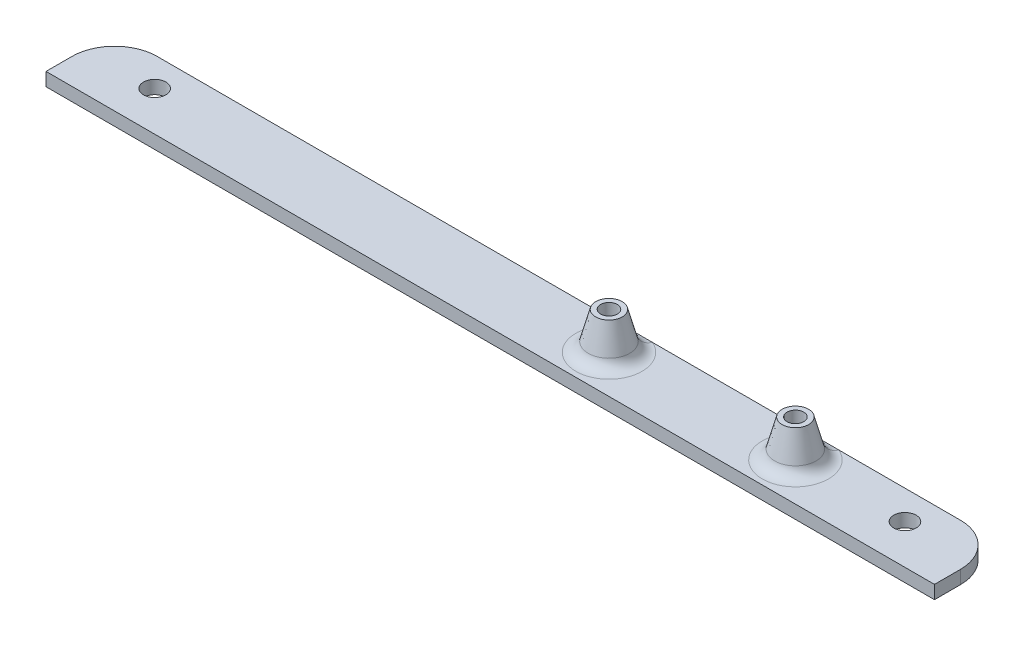
SolidWorks part; units mm, degrees
ref_plane "Front Plane" through (0, 0, 0) normal (0, 0, 1) x (1, 0, 0)
ref_plane "Top Plane" through (0, 0, 0) normal (0, 1, 0) x (1, 0, 0)
ref_plane "Right Plane" through (0, 0, 0) normal (1, 0, 0) x (0, 0, -1)
sketch "Backplane" plane through (0, 0, 0) normal (0, 1, 0) x (1, 0, 0)
  line L0 (-80.645, 87.63) -> (8.255, 87.63)
  line L1 (-106.045, -113.03) -> (106.045, -113.03)
  line L2 (-106.045, -113.03) -> (-106.045, 113.03)
  line L3 (-106.045, 113.03) -> (106.045, 113.03)
  line L4 (106.045, -113.03) -> (106.045, 113.03)
  line L5 (-106.045, -113.03) -> (106.045, 113.03) construction
  line L6 (-106.045, 113.03) -> (106.045, -113.03) construction
  line L7 (-106.045, 113.03) -> (-80.645, 113.03) construction
  line L8 (-106.045, 113.03) -> (-106.045, 87.63) construction
  line L9 (-106.045, 87.63) -> (-80.645, 87.63)
  line L10 (-80.645, 113.03) -> (-80.645, 87.63)
  line L11 (106.045, 113.03) -> (80.645, 113.03) construction
  line L12 (106.045, 113.03) -> (106.045, 87.63) construction
  line L13 (106.045, 87.63) -> (80.645, 87.63)
  line L14 (80.645, 113.03) -> (80.645, 87.63)
  line L15 (8.255, 87.63) -> (8.255, 113.03)
  line L16 (0, 0) -> (0, 113.03) construction
  line L17 (-86.8807, 106.1141) -> (86.8807, 106.1141)
  line L18 (-86.8807, 106.1141) -> (-89.5477, 106.1141)
  circle A0 centre (-89.5477, 106.1141) radius 2.667
  circle A1 centre (89.5477, 106.1141) radius 2.667
  point P0 (0, 0)
  point P19 (0, 106.1141)
  dimension "D5" = 5.334
  dimension "D1" = 212.09
  dimension "D2" = 226.06
  dimension "D3" = 173.7614
  dimension "D4" = 2.667
sketch "Protoboard1" plane through (0, 0, 0) normal (0, 1, 0) x (1, 0, 0)
  line L0 (59.2817, 74.5827) -> (59.2817, 49.1827) construction
  line L1 (-98.1983, 23.7827) -> (59.2817, 23.7827)
  line L2 (-98.1983, 23.7827) -> (-98.1983, 74.5827)
  line L3 (-98.1983, 74.5827) -> (59.2817, 74.5827)
  line L4 (59.2817, 23.7827) -> (59.2817, 74.5827)
  line L5 (-98.1983, 23.7827) -> (59.2817, 74.5827) construction
  line L6 (-98.1983, 74.5827) -> (59.2817, 23.7827) construction
  line L7 (-92.8897, 49.1827) -> (53.9731, 49.1827)
  line L8 (-19.4583, 49.1827) -> (-19.4583, 23.7827) construction
  line L9 (-92.8897, 49.1827) -> (-94.4772, 49.1827)
  circle A4 centre (-94.4772, 49.1827) radius 1.5875
  circle A5 centre (-94.4772, 49.1827) radius 5.5499
  circle A6 centre (55.5606, 49.1827) radius 1.5875
  circle A7 centre (55.5606, 49.1827) radius 5.5499
  circle A8 centre (-94.4772, 49.1827) radius 1.9939
  circle A9 centre (55.5606, 49.1827) radius 1.9939
  point P0 (-19.4583, 49.1827)
  point P9 (-19.4583, 49.1827)
  point P10 (-19.4583, 49.1827)
  dimension "D5" = 3.175
  dimension "D6" = 11.0998
  dimension "D7" = 3.9878
  dimension "D3" = 157.48
  dimension "D1" = 73.4314
  dimension "D2" = 1.5875
sketch "Protoboard2" plane through (0, 0, 0) normal (0, 1, 0) x (1, 0, 0)
  line L0 (58.42, 17.145) -> (58.42, -8.255) construction
  line L1 (-99.06, -33.655) -> (58.42, -33.655)
  line L2 (-99.06, -33.655) -> (-99.06, 17.145)
  line L3 (-99.06, 17.145) -> (58.42, 17.145)
  line L4 (58.42, -33.655) -> (58.42, 17.145)
  line L5 (-99.06, -33.655) -> (58.42, 17.145) construction
  line L6 (-99.06, 17.145) -> (58.42, -33.655) construction
  line L7 (-93.7514, -8.255) -> (53.1114, -8.255)
  line L8 (-20.32, -8.255) -> (-20.32, -33.655) construction
  line L9 (-93.7514, -8.255) -> (-95.3389, -8.255)
  circle A0 centre (-95.3389, -8.255) radius 1.5875
  circle A1 centre (-95.3389, -8.255) radius 5.5499
  circle A4 centre (-95.3389, -8.255) radius 1.9939
  circle A6 centre (54.6989, -8.255) radius 1.5875
  circle A7 centre (54.6989, -8.255) radius 1.9939
  circle A8 centre (54.6989, -8.255) radius 5.5499
  point P0 (-20.32, -8.255)
  point P9 (-20.32, -8.255)
  point P10 (-20.32, -8.255)
  dimension "D5" = 3.175
  dimension "D6" = 11.0998
  dimension "D7" = 3.9878
  dimension "D4" = 1.5875
  dimension "D1" = 157.48
  dimension "D3" = 73.4314
sketch "ADS1256" plane through (0, 0, 0) normal (0, 1, 0) x (1, 0, 0)
  line L0 (83.3697, -5.6387) -> (83.3697, 20.5868)
  line L1 (65.6786, -35.7758) -> (101.0608, -35.7758)
  line L2 (65.6786, -35.7758) -> (65.6786, 24.4984)
  line L3 (65.6786, 24.4984) -> (101.0608, 24.4984)
  line L4 (101.0608, -35.7758) -> (101.0608, 24.4984)
  line L5 (65.6786, -35.7758) -> (101.0608, 24.4984) construction
  line L6 (65.6786, 24.4984) -> (101.0608, -35.7758) construction
  line L7 (83.3697, 20.5868) -> (83.3697, 22.1743)
  line L8 (83.3697, 22.1743) -> (97.0222, 22.1743)
  line L9 (97.0222, 22.1743) -> (98.6097, 22.1743)
  line L10 (83.3697, -5.6387) -> (89.9657, -5.6387) construction
  circle A0 centre (98.6097, 22.1743) radius 1.5875
  circle A1 centre (98.6097, 22.1743) radius 5.5499
  circle A2 centre (68.1297, 22.1743) radius 1.5875
  circle A3 centre (68.1297, 22.1743) radius 5.5499
  circle A4 centre (98.6097, -33.4517) radius 5.5499
  circle A5 centre (98.6097, -33.4517) radius 1.5875
  circle A6 centre (68.1297, -33.4517) radius 1.5875
  circle A7 centre (68.1297, -33.4517) radius 5.5499
  circle A8 centre (98.6097, 22.1743) radius 1.9939
  circle A9 centre (68.1297, 22.1743) radius 1.9939
  circle A10 centre (98.6097, -33.4517) radius 1.9939
  circle A11 centre (68.1297, -33.4517) radius 1.9939
  point P0 (83.3697, -5.6387)
  dimension "D1" = 1.5875
  dimension "D2" = 1.5875
  dimension "D3" = 3.175
  dimension "D4" = 11.0998
  dimension "D5" = 3.9878
sketch "3V_Buck" plane through (0, 0, 0) normal (0, 1, 0) x (1, 0, 0)
  circle A0 centre (88.2115, 54.7666) radius 1.5875
  circle A1 centre (88.2115, 54.7666) radius 5.5499
  circle A2 centre (88.2115, 54.7666) radius 1.9939
  dimension "D1" = 3.175
  dimension "D2" = 11.0998
  dimension "D3" = 3.9878
sketch "Relay" plane through (0, 0, 0) normal (0, 1, 0) x (1, 0, 0)
  line L1 (16.3302, 81.8626) -> (66.6036, 81.8626)
  line L2 (16.3302, 81.8626) -> (16.3302, 108.1272)
  line L3 (16.3302, 108.1272) -> (66.6036, 108.1272)
  line L4 (66.6036, 81.8626) -> (66.6036, 108.1272)
  line L5 (16.3302, 81.8626) -> (66.6036, 108.1272) construction
  line L6 (16.3302, 108.1272) -> (66.6036, 81.8626) construction
  line L7 (41.4669, 94.9949) -> (41.4669, 104.2024)
  line L8 (41.4669, 104.2024) -> (41.4669, 105.7899)
  line L9 (41.4669, 105.7899) -> (62.1298, 105.7899)
  line L10 (62.1298, 105.7899) -> (63.7173, 105.7899)
  line L11 (41.4669, 94.9949) -> (31.7125, 94.9949) construction
  circle A0 centre (63.7173, 105.7899) radius 1.5875
  circle A1 centre (63.7173, 105.7899) radius 5.5499
  circle A2 centre (19.2165, 105.7899) radius 1.5875
  circle A3 centre (19.2165, 105.7899) radius 5.5499
  circle A4 centre (19.2165, 84.1999) radius 1.5875
  circle A5 centre (19.2165, 84.1999) radius 5.5499
  circle A6 centre (63.7173, 84.1999) radius 1.5875
  circle A7 centre (63.7173, 84.1999) radius 5.5499
  circle A8 centre (63.7173, 105.7899) radius 1.9939
  circle A9 centre (19.2165, 105.7899) radius 1.9939
  circle A10 centre (19.2165, 84.1999) radius 1.9939
  circle A11 centre (63.7173, 84.1999) radius 1.9939
  dimension "D4" = 3.175
  dimension "D5" = 11.0998
  dimension "D6" = 3.9878
  dimension "D1" = 1.5875
  dimension "D2" = 20.6629
  dimension "D3" = 1.5875
sketch "ServoBoard" plane through (0, 0, 0) normal (0, 1, 0) x (1, 0, 0)
  line L0 (-89.6011, -103.339) -> (-89.6011, -58.0508)
  line L1 (-103.5076, -105.5869) -> (-34.6228, -105.5869)
  line L2 (-103.5076, -105.5869) -> (-103.5076, -52.1961)
  line L3 (-103.5076, -52.1961) -> (-34.6228, -52.1961)
  line L4 (-34.6228, -105.5869) -> (-34.6228, -52.1961)
  line L5 (-103.5076, -105.5869) -> (-34.6228, -52.1961) construction
  line L6 (-103.5076, -52.1961) -> (-34.6228, -105.5869) construction
  line L7 (-103.5076, -105.5869) -> (-91.1886, -105.5869)
  line L8 (-103.5076, -105.5869) -> (-103.5076, -104.9265)
  line L9 (-103.5076, -104.9265) -> (-91.1886, -104.9265)
  line L10 (-91.1886, -105.5869) -> (-91.1886, -104.9265)
  line L11 (-91.1886, -104.9265) -> (-89.6011, -104.9265)
  line L12 (-91.1886, -104.9265) -> (-91.1886, -103.339)
  line L13 (-91.1886, -103.339) -> (-89.6011, -103.339)
  line L14 (-89.6011, -104.9265) -> (-89.6011, -103.339)
  line L15 (-89.6011, -58.0508) -> (-89.6011, -54.8758)
  line L16 (-89.6011, -103.339) -> (-38.6137, -69.1904)
  line L17 (-89.6011, -54.8758) -> (-38.6134, -69.1905)
  circle A0 centre (-89.6011, -103.339) radius 1.651
  circle A1 centre (-89.6011, -103.339) radius 1.9939
  circle A2 centre (-89.6011, -103.339) radius 5.5499
  circle A3 centre (-89.6011, -54.8758) radius 1.5875
  circle A4 centre (-89.6011, -54.8758) radius 1.9939
  circle A5 centre (-89.6011, -54.8758) radius 5.5499
  circle A6 centre (-38.6134, -69.1905) radius 1.5875
  circle A7 centre (-38.6137, -69.1904) radius 1.9939
  circle A8 centre (-38.6137, -69.1904) radius 5.5499
  point P0 (-69.0652, -78.8915)
  dimension "D3" = 1.5875
  dimension "D8" = 3.9878
  dimension "D9" = 11.0998
  dimension "D11" = 3.175
  dimension "D12" = 3.9878
  dimension "D13" = 11.0998
  dimension "D7" = 3.302
  dimension "D17" = 3.175
  dimension "D18" = 3.9878
  dimension "D19" = 11.0998
  dimension "D1" = 68.8848
  dimension "D2" = 53.3908
  dimension "D4" = 1.5875
  dimension "D5" = 12.319
  dimension "D6" = 0.6604
  dimension "D10" = 3.175
  dimension "D14" = 45.2882
  dimension "D15" = 74.318
  dimension "D16" = 56.188
sketch "Nucleo" plane through (0, 0, 0) normal (0, 1, 0) x (1, 0, 0)
  line L0 (73.7198, -98.0391) -> (73.7198, -49.7791)
  line L1 (-30.5599, -110.32) -> (102.7901, -110.32)
  line L2 (-30.5599, -110.32) -> (-30.5599, -40.6732)
  line L3 (-30.5599, -40.6732) -> (102.7901, -40.6732)
  line L4 (102.7901, -110.32) -> (102.7901, -40.6732)
  line L5 (-30.5599, -110.32) -> (102.7901, -40.6732) construction
  line L6 (-30.5599, -40.6732) -> (102.7901, -110.32) construction
  line L11 (102.7901, -110.32) -> (75.3073, -110.32)
  line L12 (102.7901, -110.32) -> (102.7901, -99.6266)
  line L13 (102.7901, -99.6266) -> (75.3073, -99.6266)
  line L14 (75.3073, -110.32) -> (75.3073, -99.6266)
  line L15 (75.3073, -99.6266) -> (73.7198, -99.6266)
  line L16 (75.3073, -99.6266) -> (75.3073, -98.0391)
  line L17 (75.3073, -98.0391) -> (73.7198, -98.0391)
  line L18 (73.7198, -99.6266) -> (73.7198, -98.0391)
  line L19 (73.7198, -98.0391) -> (-1.2702, -98.0391)
  line L20 (-1.2702, -98.0391) -> (-1.2702, -96.7691)
  line L21 (-1.2702, -96.7691) -> (-1.2702, -51.0491)
  circle A0 centre (73.7198, -98.0391) radius 1.5875
  circle A1 centre (73.7198, -98.0391) radius 1.9939
  circle A2 centre (73.7198, -98.0391) radius 5.5499
  circle A3 centre (73.7198, -49.7791) radius 1.5875
  circle A4 centre (73.7198, -49.7791) radius 1.9939
  circle A5 centre (73.7198, -49.7791) radius 5.5499
  circle A6 centre (-1.2702, -96.7691) radius 1.5875
  circle A7 centre (-1.2702, -96.7691) radius 1.9939
  circle A8 centre (-1.2702, -96.7691) radius 5.5499
  circle A9 centre (-1.2702, -51.0491) radius 1.5875
  circle A10 centre (-1.2702, -51.0491) radius 1.9939
  circle A11 centre (-1.2702, -51.0491) radius 5.5499
  point P0 (36.1151, -75.4966)
  dimension "D1" = 1.5875
  dimension "D2" = 1.5875
  dimension "D7" = 3.175
  dimension "D8" = 3.9878
  dimension "D9" = 11.0998
  dimension "D11" = 3.175
  dimension "D12" = 3.9878
  dimension "D13" = 11.0998
  dimension "D16" = 3.175
  dimension "D17" = 3.9878
  dimension "D18" = 11.0998
  dimension "D20" = 3.175
  dimension "D21" = 3.9878
  dimension "D22" = 11.0998
  dimension "D3" = 133.35
  dimension "D4" = 69.6468
  dimension "D5" = 27.4828
  dimension "D6" = 10.6934
  dimension "D10" = 48.26
  dimension "D14" = 74.99
  dimension "D15" = 1.27
  dimension "D19" = 45.72
extrude "Backplane_Extrude" add sketch "Backplane" against normal blind 3.175 contours L17 L15 L0 L9 L2 L1 L4 L13 L14 | L17 L10 L0 L15 | L10 L17 L15 L3 | L15 L17 L14 L3 | A1 L14 L13 L4 L3 | A0 L10 L3 L2 L9 region at (-36.195, 0, -96.872) region at (1.3549, 0, 9.36) region at (-93.4812, 0, -100.1225) region at (-36.195, 0, -109.572) region at (44.45, 0, -109.572) region at (93.4812, 0, -100.1225)
fillet "Backplane_Fillets" radius 10.16 4 edges at (106.045, -1.5875, 113.03) (-106.045, -1.5875, 113.03) (106.045, -1.5875, -113.03) (-106.045, -1.5875, -113.03)
extrude "Boss-Extrude2" add sketch "Protoboard1" along normal blind 8.89 contours A8 A5 L2 | L2 A5 | A9 A7 L4 | A7 L4 region at (-98.9412, 0, -49.1827) region at (-98.0536, 0, -49.1827) region at (53.3666, 0, -44.2427) region at (60.0247, 0, -49.1827)
draft "Draft1" type of draft neutral plane draft angle 15 faces to draft 2 face at (55.5606, 8.89, -43.6328) face at (-94.4772, 8.89, -43.6328) neutral plane through (0, 0, 0) neutral plane normal (0, 1, 0) parameters "D1"=15
fillet "Fillet5" radius 3.048 2 edges at (55.5606, 0, -43.6328) (-94.4772, 0, -43.6328)
extrude "Boss-Extrude3" add sketch "Protoboard2" along normal blind 8.89 contours A4 A1 L2 | L2 A1 | A8 A7 L4 | A8 L4 region at (-99.8029, 0, 8.255) region at (-98.9154, 0, 8.255) region at (52.5049, 0, 13.195) region at (59.1629, 0, 8.255)
draft "Draft2" type of draft neutral plane draft angle 15 faces to draft 2 face at (54.6989, 8.89, 13.8049) face at (-95.3389, 8.89, 13.8049) neutral plane through (0, 0, 0) neutral plane normal (0, 1, 0) parameters "D1"=15
fillet "Fillet6" radius 3.048 2 edges at (54.6989, 0, 13.8049) (-95.3389, 0, 13.8049)
extrude "Boss-Extrude4" add sketch "ADS1256" along normal blind 8.89 contours A3 L3 L2 A9 | A3 L2 L3 | L4 A1 L3 | A8 A1 L4 L3 | A4 L4 L1 | A4 L1 L4 A10 | L1 A7 L2 A11 | L2 A7 L1 region at (69.706, 0, 31.7947) region at (69.4241, 0, 35.9251) region at (97.0334, 0, 31.7947) region at (97.3153, 0, 35.9251) region at (64.3596, 0, -26.0412) region at (69.706, 0, -20.5173) region at (97.0334, 0, -20.5173) region at (101.2101, 0, -20.8467)
draft "Draft3" type of draft neutral plane draft angle 15 faces to draft 4 face at (98.6097, 8.89, -16.6244) face at (98.6097, 8.89, 39.0016) face at (68.1297, 8.89, 39.0016) face at (68.1297, 8.89, -16.6244) neutral plane through (0, 0, 0) neutral plane normal (0, 1, 0) parameters "D1"=15
fillet "Fillet7" radius 3.048 4 edges at (98.6097, 0, 39.0016) (98.6097, 0, -16.6244) (68.1297, 0, -16.6244) (68.1297, 0, 39.0016)
extrude "Boss-Extrude5" add sketch "3V_Buck" along normal blind 8.89 contours A1 A2 region at (82.8185, 0, -54.7666)
draft "Draft4" type of draft neutral plane draft angle 15 faces to draft 1 face at (88.2115, 8.89, -49.2167) neutral plane through (0, 0, 0) neutral plane normal (0, 1, 0) parameters "D1"=15
fillet "Fillet8" radius 3.048 1 edges at (88.2115, 0, -49.2167)
extrude "Boss-Extrude6" add sketch "Relay" along normal blind 8.89 contours A3 L3 L2 A9 | A3 L2 L3 | A8 A1 L4 L3 | L4 A1 L3 | A7 L4 L1 | A7 L1 L4 A11 | L1 A5 L2 A10 | L2 A5 L1 region at (20.5049, 0, -85.8218) region at (20.2902, 0, -81.715) region at (62.429, 0, -85.8218) region at (62.6436, 0, -81.715) region at (15.6168, 0, -109.8181) region at (20.5049, 0, -104.168) region at (62.429, 0, -104.168) region at (66.7513, 0, -104.5884)
draft "Draft5" type of draft neutral plane draft angle 15 faces to draft 4 face at (19.2165, 8.89, -78.65) face at (63.7173, 8.89, -78.65) face at (63.7173, 8.89, -100.24) face at (19.2165, 8.89, -100.24) neutral plane through (0, 0, 0) neutral plane normal (0, 1, 0) parameters "D1"=15
fillet "Fillet9" radius 3.048 4 edges at (19.2165, 0, -78.65) (63.7173, 0, -78.65) (63.7173, 0, -100.24) (19.2165, 0, -100.24)
extrude "Boss-Extrude7" add sketch "ServoBoard" along normal blind 8.89 contours L0 A5 L17 A4 L15 | L17 A5 L3 L0 L15 A4 | L3 A5 | L4 A8 | L4 A8 L17 A7 L16 | L17 A8 L16 A7 | L1 A2 L16 A1 L11 L10 | L7 A2 L1 | L0 A2 L9 L12 A1 | L16 A2 L0 A1 | L9 A2 L7 L10 region at (-92.4087, 0, 101.4937) region at (-87.7688, 0, 99.9065) region at (-86.2185, 0, 103.5104) region at (-94.2609, 0, 57.6277) region at (-87.3219, 0, 57.8828) region at (-92.9975, 0, 105.253) region at (-42.4911, 0, 69.809) region at (-41.6669, 0, 71.4099) region at (-89.6011, 0, 51.018) region at (-89.6011, 0, 106.9485) region at (-33.991, 0, 69.1904)
draft "Draft6" type of draft neutral plane draft angle 15 faces to draft 3 face at (-89.6011, 8.89, 60.4257) face at (-38.6137, 8.89, 74.7403) face at (-89.6011, 8.89, 108.8889) neutral plane through (0, 0, 0) neutral plane normal (0, 1, 0) parameters "D1"=15
fillet "Fillet10" radius 3.048 3 edges at (-89.6011, 0, 108.8889) (-38.6137, 0, 74.7403) (-89.6011, 0, 60.4257)
extrude "Boss-Extrude8" add sketch "Nucleo" along normal blind 8.89 contours A11 A10 | A5 A4 | L13 A2 L0 A1 L16 | L0 A2 L19 A1 | L19 A2 L14 L15 A1 | L14 A2 L13 | L21 A8 L19 A7 | L19 A8 L21 A7 region at (71.1407, 0, 95.46) region at (76.5275, 0, 96.1938) region at (71.8745, 0, 100.8467) region at (69.9064, 0, 45.9657) region at (-5.0836, 0, 47.2357) region at (-5.4982, 0, 100.1185) region at (1.5063, 0, 94.7714) region at (76.7573, 0, 101.0766)
draft "Draft7" type of draft neutral plane draft angle 15 faces to draft 4 face at (73.7198, 8.89, 103.589) face at (73.7198, 8.89, 55.329) face at (-1.2702, 8.89, 56.599) face at (-1.2702, 8.89, 102.319) neutral plane through (0, 0, 0) neutral plane normal (0, 1, 0) parameters "D1"=15
fillet "Fillet11" radius 3.048 4 edges at (73.7198, 0, 103.589) (73.7198, 0, 55.329) (-1.2702, 0, 56.599) (-1.2702, 0, 102.319)
sketch "Sketch1" plane through (0, 0, 0) normal (0, 1, 0) x (1, 0, 0)
  line L1 (-110.9974, 121.3264) -> (108.5308, 121.3264)
  line L2 (-110.9974, 121.3264) -> (-110.9974, 96.6603)
  line L3 (-110.9974, 96.6603) -> (108.5308, 96.6603)
  line L4 (108.5308, 121.3264) -> (108.5308, 96.6603)
extrude "Cut-Extrude1" cut sketch "Sketch1" against normal mid plane 50.8 flip side to cut
equation "\"D4@Backplane\"=.210/2"
equation "\"D2@Relay\"=1.627/2"
equation "\"D1@Protoboard1\" = 5.782 / 2"
equation "\"M3_PCB_Hole_Diam\"= 0.125in"
equation "\"M3_Insert_OuterFeature_Diam\"= \"M3_Print_CAD_Hole_Diam\" + ( 0.14 * 2 )"
equation "\"D2@Protoboard1\" = \"M3_PCB_Hole_Diam\" / 2"
equation "\"D5@Protoboard1\" = \"M3_PCB_Hole_Diam\""
equation "\"D6@Protoboard1\" = \"M3_Insert_OuterFeature_Diam\""
equation "\"D1@Relay\"=\"M3_PCB_Hole_Diam\"/2"
equation "\"D3@Relay\"=\"M3_PCB_Hole_Diam\"/2"
equation "\"D4@Relay\"=\"M3_PCB_Hole_Diam\""
equation "\"D5@Relay\"=\"M3_Insert_OuterFeature_Diam\""
equation "\"D1@ADS1256\"=\"M3_PCB_Hole_Diam\"/2"
equation "\"D2@ADS1256\"=\"M3_PCB_Hole_Diam\"/2"
equation "\"D3@ADS1256\"=\"M3_PCB_Hole_Diam\""
equation "\"D4@ADS1256\"=\"M3_Insert_OuterFeature_Diam\""
equation "\"M3_Print_CAD_Hole_Diam\"= 0.157in"
equation "\"D5@ADS1256\"=\"M3_Print_CAD_Hole_Diam\""
equation "\"D7@Protoboard1\" = \"M3_Print_CAD_Hole_Diam\""
equation "\"D6@Relay\"=\"M3_Print_CAD_Hole_Diam\""
equation "\"D3@3V_Buck\"=\"M3_Print_CAD_Hole_Diam\""
equation "\"D1@3V_Buck\"=\"M3_PCB_Hole_Diam\""
equation "\"D1@Nucleo\"=\"M3_PCB_Hole_Diam\"/2"
equation "\"D2@Nucleo\"=\"M3_PCB_Hole_Diam\"/2"
equation "\"D7@Nucleo\"=\"M3_PCB_Hole_Diam\""
equation "\"D8@Nucleo\"=\"M3_Print_CAD_Hole_Diam\""
equation "\"D9@Nucleo\"=\"M3_Insert_OuterFeature_Diam\""
equation "\"D11@Nucleo\"=\"M3_PCB_Hole_Diam\""
equation "\"D12@Nucleo\"=\"M3_Print_CAD_Hole_Diam\""
equation "\"D13@Nucleo\"=\"M3_Insert_OuterFeature_Diam\""
equation "\"D16@Nucleo\"=\"M3_PCB_Hole_Diam\""
equation "\"D17@Nucleo\"=\"M3_Print_CAD_Hole_Diam\""
equation "\"D18@Nucleo\"=\"M3_Insert_OuterFeature_Diam\""
equation "\"D20@Nucleo\"=\"M3_PCB_Hole_Diam\""
equation "\"D21@Nucleo\"=\"M3_Print_CAD_Hole_Diam\""
equation "\"D22@Nucleo\"=\"M3_Insert_OuterFeature_Diam\""
equation "\"D14@Nucleo\"=133.4mm-12.7mm-16.51mm-3.8mm-2.54mm-22.86mm"
equation "\"D19@Nucleo\"=45.72mm"
equation "\"D3@ServoBoard\"=\"M3_PCB_Hole_Diam\"/2"
equation "\"D4@ServoBoard\"=\"M3_PCB_Hole_Diam\"/2"
equation "\"D8@ServoBoard\"=\"M3_Print_CAD_Hole_Diam\""
equation "\"D9@ServoBoard\"=\"M3_Insert_OuterFeature_Diam\""
equation "\"D10@ServoBoard\"=\"M3_PCB_Hole_Diam\""
equation "\"D11@ServoBoard\"=\"M3_PCB_Hole_Diam\""
equation "\"D12@ServoBoard\"=\"M3_Print_CAD_Hole_Diam\""
equation "\"D13@ServoBoard\"=\"M3_Insert_OuterFeature_Diam\""
equation "\"D17@ServoBoard\"=\"M3_PCB_Hole_Diam\""
equation "\"D18@ServoBoard\"=\"M3_Print_CAD_Hole_Diam\""
equation "\"D19@ServoBoard\"=\"M3_Insert_OuterFeature_Diam\""
equation "\"M3_Insert_OuterFeature_DraftAngle\"= 15deg"
equation "\"D1@Draft1\"=\"M3_Insert_OuterFeature_DraftAngle\""
equation "\"M3_Insert_OuterFeature_FilletRad\"= 0.12in"
equation "\"D1@Fillet5\"=\"M3_Insert_OuterFeature_FilletRad\""
equation "\"M3_Insert_OuterFeature_ExtrudeHt\"= 0.35in"
equation "\"D1@Boss-Extrude2\"=\"M3_Insert_OuterFeature_ExtrudeHt\""
equation "\"D6@Protoboard2\"=\"M3_Insert_OuterFeature_Diam\""
equation "\"D5@Protoboard2\"=\"M3_PCB_Hole_Diam\""
equation "\"D7@Protoboard2\"=\"M3_Print_CAD_Hole_Diam\""
equation "\"D1@Boss-Extrude3\"=\"M3_Insert_OuterFeature_ExtrudeHt\""
equation "\"D1@Draft2\"=\"M3_Insert_OuterFeature_DraftAngle\""
equation "\"D1@Fillet6\"=\"M3_Insert_OuterFeature_FilletRad\""
equation "\"D1@Boss-Extrude4\"=\"M3_Insert_OuterFeature_ExtrudeHt\""
equation "\"D1@Draft3\"=\"M3_Insert_OuterFeature_DraftAngle\""
equation "\"D1@Fillet7\"=\"M3_Insert_OuterFeature_FilletRad\""
equation "\"D1@Boss-Extrude5\"=\"M3_Insert_OuterFeature_ExtrudeHt\""
equation "\"D1@Draft4\"=\"M3_Insert_OuterFeature_DraftAngle\""
equation "\"D2@3V_Buck\"=\"M3_Insert_OuterFeature_Diam\""
equation "\"D1@Fillet8\"=\"M3_Insert_OuterFeature_FilletRad\""
equation "\"D1@Boss-Extrude6\"=\"M3_Insert_OuterFeature_ExtrudeHt\""
equation "\"D1@Draft5\"=\"M3_Insert_OuterFeature_DraftAngle\""
equation "\"D1@Fillet9\"=\"M3_Insert_OuterFeature_FilletRad\""
equation "\"D1@Boss-Extrude7\"=\"M3_Insert_OuterFeature_ExtrudeHt\""
equation "\"D1@Draft6\"=\"M3_Insert_OuterFeature_DraftAngle\""
equation "\"D1@Fillet10\"=\"M3_Insert_OuterFeature_FilletRad\""
equation "\"D1@Boss-Extrude8\"=\"M3_Insert_OuterFeature_ExtrudeHt\""
equation "\"D1@Fillet11\"=\"M3_Insert_OuterFeature_FilletRad\""
equation "\"D1@Draft7\"=\"M3_Insert_OuterFeature_DraftAngle\""
